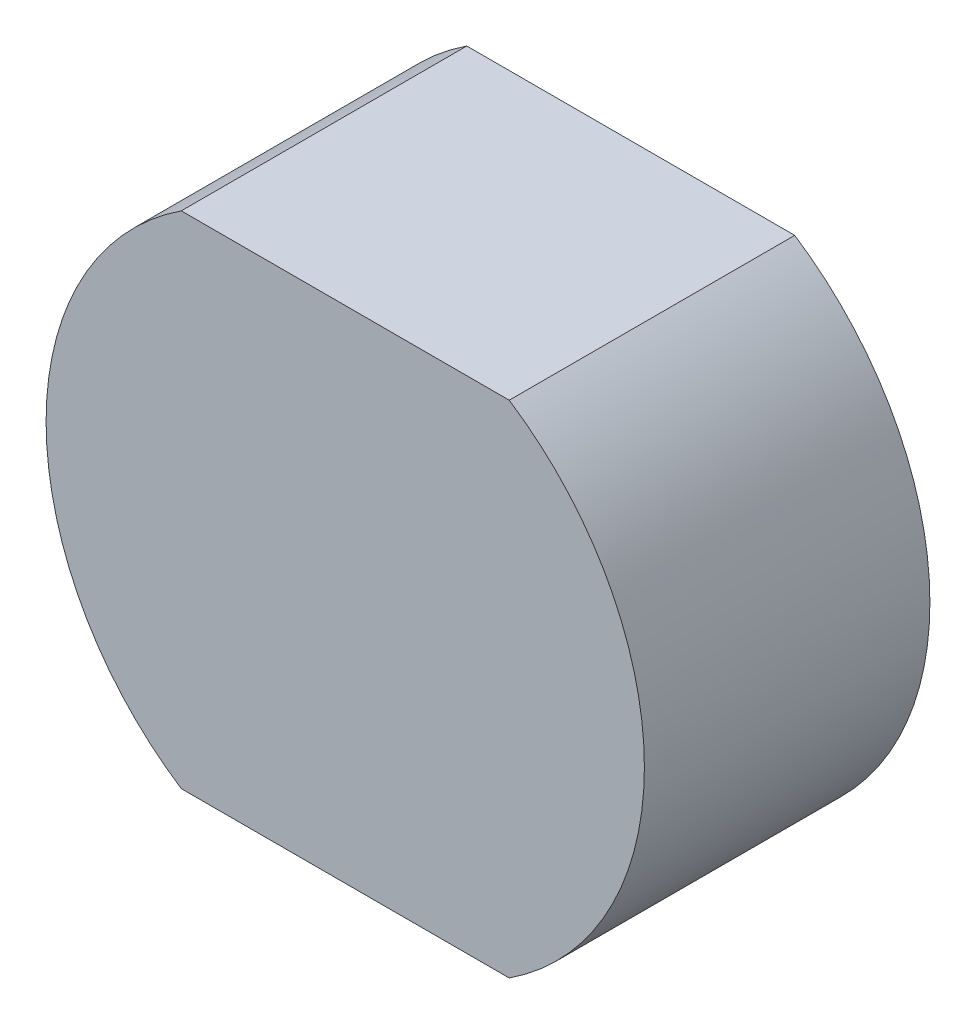
SolidWorks part; units mm, degrees
ref_plane "Front Plane" through (0, 0, 0) normal (0, 0, 1) x (1, 0, 0)
ref_plane "Top Plane" through (0, 0, 0) normal (0, 1, 0) x (1, 0, 0)
ref_plane "Right Plane" through (0, 0, 0) normal (1, 0, 0) x (0, 0, -1)
sketch "Sketch1" plane through (0, 0, 0) normal (0, 0, 1) x (1, 0, 0)
  line L0 (-1.1487, 1.7526) -> (1.1487, 1.7526)
  line L1 (-1.1487, -1.7526) -> (1.1487, -1.7526)
  line L3 (-6.3373, 1.7526) -> (9.6223, 1.7526) construction
  line L4 (-6.3373, -1.7526) -> (9.6223, -1.7526) construction
  arc A0 (-1.1487, 1.7526) -> (-1.1487, -1.7526) centre (0, 0) ccw
  arc A1 (1.1487, -1.7526) -> (1.1487, 1.7526) centre (0, 0) ccw
  dimension "D1" = 1.7526
  dimension "D3" = 2.0955
  dimension "D2" = 3.5052
extrude "Boss-Extrude1" add sketch "Sketch1" along normal blind 1 and the other way blind 1
